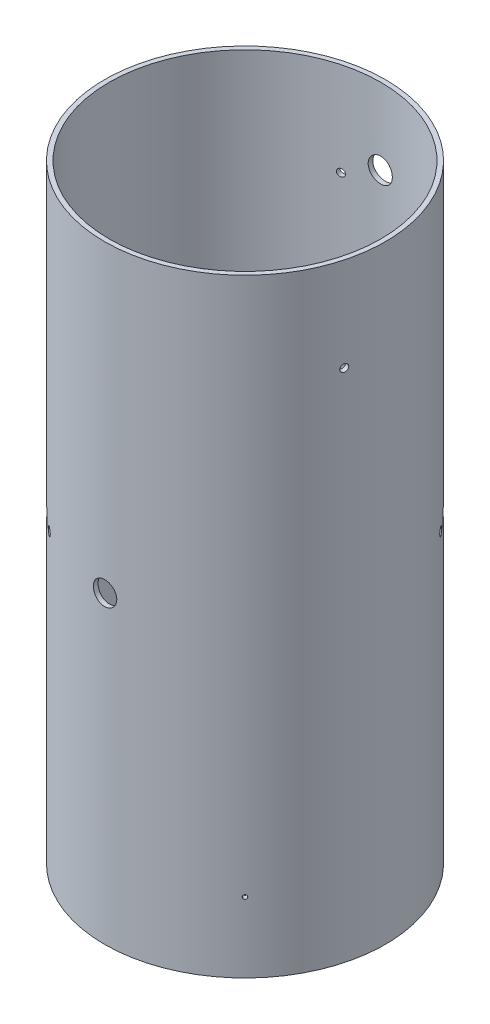
SolidWorks part; units mm, degrees
material "A-Glass Fiber"
ref_plane "Front Plane" through (0, 0, 0) normal (0, 0, 1) x (1, 0, 0)
ref_plane "Top Plane" through (0, 0, 0) normal (0, 1, 0) x (1, 0, 0)
ref_plane "Right Plane" through (0, 0, 0) normal (1, 0, 0) x (0, 0, -1)
sketch "Sketch1" plane through (0, 0, 0) normal (0, 1, 0) x (1, 0, 0)
  circle A0 centre (0, 0) radius 76.1746
  circle A1 centre (0, 0) radius 73.66
  dimension "D1" = 152.3492
  dimension "D2" = 147.32
extrude "Boss-Extrude1" add sketch "Sketch1" along normal blind 330.2
sketch "Sketch4" plane through (0, 0, 0) normal (0, 0, 1) x (1, 0, 0)
  line L0 (-76.1746, 0) -> (76.1746, 0) construction
  line L1 (76.1746, 330.2) -> (-76.1746, 330.2) construction
  line L2 (0, 330.2) -> (0, 0) construction
  line L3 (73.66, 330.2) -> (-73.66, 330.2) construction
  point P0 (0, 41.275)
  point P3 (0, 288.925)
  dimension "D1" = 41.275
  dimension "D2" = 41.275
hole_wizard "1/2 Clearance Hole5" positions "Sketch16" profile "Sketch17" hole size "1/2" standard "ANSI Inch"
sketch "Sketch16" plane through (0, 0, 0) normal (0, 0, 1) x (1, 0, 0)
  point P0 (0, 288.925)
sketch "Sketch17" plane through (0, 288.925, 0) normal (1, 0, 0) x (0, -1, 0)
  line L0 (0, 0) -> (0, 80.1345)
  line L1 (0, 80.1345) -> (6.5481, 76.2)
  line L2 (6.5481, 76.2) -> (6.5481, 0)
  line L5 (6.5481, 0) -> (0, 0)
  line L10 (0, 80.1345) -> (-6.5481, 76.2) construction
  line L11 (0, -6.35) -> (0, 107.95) construction
  dimension "Hole Dia." = 13.0962
  dimension "Hole Depth" = 76.2
  dimension "Drill Angle" = 118
sketch "Sketch27" plane through (0, 0, 0) normal (0, 0, 1) x (1, 0, 0)
  line L0 (0, 330.2) -> (0, 0) construction
  line L1 (-76.1746, 0) -> (76.1746, 0) construction
  circle A0 centre (0, 165.1) radius 6.35
  dimension "D1" = 12.7
  dimension "D2" = 165.1
extrude "Cut-Extrude1" cut sketch "Sketch27" against normal through all both and the other way through all
ref_plane "Plane1" through (0, 0, 0) normal (-0.7071, 0, 0.7071) x (0.7071, 0, 0.7071)
ref_plane "Plane2" through (0, 0, 0) normal (-0.7071, 0, 0.7071) x (0, -1, 0)
sketch "Sketch30" plane through (0, 0, 0) normal (-0.7071, 0, 0.7071) x (0.7071, 0, 0.7071)
  line L0 (0, 330.2) -> (0, 0) construction
  line L1 (4.953, 160.147) -> (-4.953, 160.147)
  line L2 (4.953, 160.147) -> (4.953, 170.053)
  line L3 (4.953, 170.053) -> (-4.953, 170.053)
  line L4 (-4.953, 160.147) -> (-4.953, 170.053)
  line L5 (4.953, 160.147) -> (-4.953, 170.053) construction
  line L6 (4.953, 170.053) -> (-4.953, 160.147) construction
  line L7 (-76.1746, 0) -> (76.1746, 0) construction
  circle A0 centre (-12.7, 165.1) radius 2.1831
  circle A1 centre (12.7, 165.1) radius 2.1831
  point P0 (0, 165.1)
  dimension "D3" = 4.3663
  dimension "D4" = 4.3663
  dimension "D1" = 9.906
  dimension "D2" = 9.906
  dimension "D5" = 12.7
  dimension "D6" = 12.7
  dimension "D7" = 165.1
extrude "Cut-Extrude2" cut sketch "Sketch30" against normal through all both and the other way through all
sketch "Sketch23" plane through (0, 0, 0) normal (-0.7071, 0, 0.7071) x (0.7071, 0, 0.7071)
  line L0 (0, 0) -> (0, 330.2) construction
  line L1 (73.66, 330.2) -> (-73.66, 330.2) construction
  line L2 (-76.1746, 165.1) -> (76.1746, 165.1) construction
  line L3 (76.1746, 0) -> (76.1746, 330.2) construction
  circle A1 centre (0, 38.1) radius 1.0922
  point P12 (0, 165.1)
  dimension "D2" = 127
extrude "Shear Scrrews" cut sketch "Sketch23" against normal through all
pattern_circular "CirPattern1" count 4 over 360 about axis through (0, 330.2, 0) along (0, -1, 0) of "Shear Scrrews"
hole_wizard "Ø4.0 (4) Diameter Hole1" positions "Sketch24" profile "Sketch25" hole size "Ø4.0" standard "ANSI Metric"
sketch "Sketch24" plane through (0, 0, 0) normal (-0.7071, 0, 0.7071) x (0, -1, 0)
  line L0 (-330.2, 76.1746) -> (-330.2, -76.1746) construction
  point P0 (-279.4, 0)
  dimension "D1" = 50.8
sketch "Sketch25" plane through (0, 279.4, 0) normal (0, 1, 0) x (-0.7071, 0, -0.7071)
  line L0 (0, 0) -> (0, 90.1017)
  line L1 (0, 90.1017) -> (2, 88.9)
  line L2 (2, 88.9) -> (2, 0)
  line L5 (2, 0) -> (0, 0)
  line L10 (0, 90.1017) -> (-2, 88.9) construction
  line L11 (0, -6.35) -> (0, 107.95) construction
  dimension "Hole Dia." = 4
  dimension "Hole Depth" = 88.9
  dimension "Drill Angle" = 118
pattern_circular "CirPattern2" count 3 over 360 about axis through (0, 330.2, 0) along (0, 1, 0) of "Ø4.0 (4) Diameter Hole1"
equation "\"Mid_Coupler_Length\" = 13in"
equation "\"D1@Boss-Extrude1\"=\"Mid_Coupler_Length\""
equation "\"Shear_Screw_Coupler_Location\" = 4.5in"
equation "\"Shear_Screw_Diameter\" = 0.086in"
equation "\"D2@Sketch23\"=\"Shear_Screw_Coupler_Location\"+0.5"
equation "\"Mid_Tube_Length\"= 1in"
equation "\"Bodytube_OD\" = 6.17in"
equation "\"Bodytube_ID\" = 5.998in"
equation "\"Camera_Cutout_Width\"=10mm"
equation "\"Camera_Cutout_Height\"=7mm"
equation "\"Fwd_Tube_Length\" = 38.5in"
equation "\"BKHD_Screw_Diam\"= 3.5mm"
equation "\"Fwd_BKHD_From_Top\" = 18in"
equation "\"Motor_OD\" = 4in"
equation "\"Aft_Section_Length\"= 36in"
equation "\"AB_Coupler_OD_Length\"= 1in"
equation "\"AB_Coupling_Section_Length\"= 0.375in"
equation "\"AB_Coupler_Length\"= \"AB_Coupler_OD_Length\" + \"AB_Coupling_Section_Length\" * 2"
equation "\"Cutout_Angle\" = 80"
equation "\"AB_Paddle_Height\" = 0.375in"
equation "\"AB_Coupler_Num_Screws\"= 4"
equation "\"AB_BKHD_Thickness\" = 0.375in"
equation "\"AB_Mount_From_Bottom\" = 23.175in"
equation "\"Num_Cutouts\" = 3"
equation "\"AB_Coupler_OD\"= 6.17in"
equation "\"AB_Coupler_ID\"= 5.75in"
equation "\"AB_Coupler_Surface_Diameter\"= 5.998in"
equation "\"AB_Coupling_Screw_Diameter\"= 0.15748in"
equation "\"AB_Central_Bushing_Length\" = .4724in"
equation "\"Lead_Screw_Dist\" = 3.4in"
equation "\"Lead_Screw_Diam\" = 0.386in"
equation "\"Lead_Screw_Length\" = (\"Mid_Coupler_Length\" + 2*0.375in + 2*.75in)"
equation "\"Paddle_Pin_Offset\" = .25in"
equation "\"Paddle_Pin_Radius\" = 2.25in"
equation "\"SS_Paddle_Pin_Radius\" = 2.25*0.66in"
equation "\"Paddle_Gear_OD\" = 3.2in"
equation "\"Drive_Gear_OD\" = 1.7in"
equation "\"Fin_Thickness\"= .118in"
equation "\"Guiderail_Cutout_Diameter\"= 1.5in"
equation "\"DB9_Hole_Dist\" = 25mm"
equation "\"DB9_Relief_Width\" = 0.47in"
equation "\"DB9_Relief_Hole_Offset\" = 0.09in"
equation "\"Airbrakes_Wire_Hole_Dia\" = .25in"
equation "\"Airbrakes_Wire_Hole_Dist\" = 1.1in"
equation "\"Servo_Gear_Offset\" = 0.5in"
equation "\"FWD_Shear_Screw_Dist\" = 1.5in"
equation "\"Camera_Screw_Dia\" = 0.216535"
equation "\"Camera_Hole_Angle\" = atn ( 2 / 3 * tan ( 12.5deg ) )"
equation "\"D2\"= \"Camera_Hole_Angle\""
equation "\"Coupler_OD\" = 5.998"
equation "\"D1@Sketch1\"=\"Coupler_OD\""
equation "\"Coupler_ID\" = 5.8"
equation "\"D2@Sketch1\"=\"Coupler_ID\""
